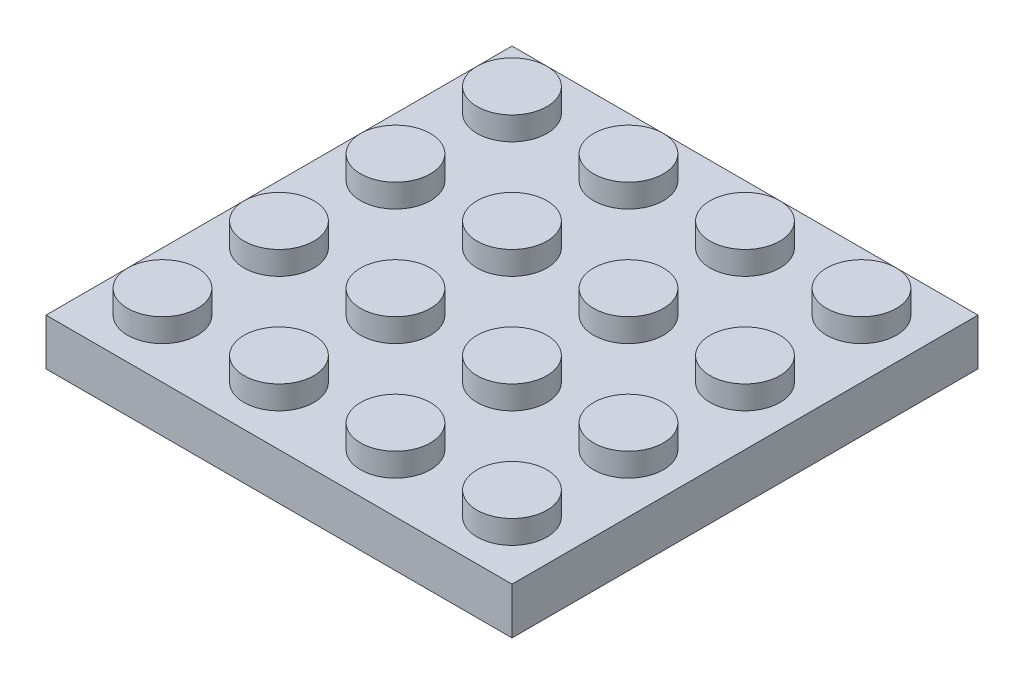
SolidWorks part; units mm, degrees
ref_plane "Front Plane" through (0, 0, 0) normal (0, 0, 1) x (1, 0, 0)
ref_plane "Top Plane" through (0, 0, 0) normal (0, 1, 0) x (1, 0, 0)
ref_plane "Right Plane" through (0, 0, 0) normal (1, 0, 0) x (0, 0, -1)
sketch "Sketch1" plane through (0, 0, 0) normal (0, 1, 0) x (1, 0, 0)
  line L0 (2.5, 12.5) -> (7.5, 17.5)
  line L1 (0, 0) -> (20, 0)
  line L2 (0, 0) -> (0, 20)
  line L3 (0, 20) -> (20, 20)
  line L4 (20, 0) -> (20, 20)
  line L5 (0, 20) -> (2.5, 20)
  line L6 (0, 20) -> (0, 17.5)
  line L7 (0, 17.5) -> (2.5, 17.5)
  line L8 (2.5, 20) -> (2.5, 17.5)
  line L9 (1, 1) -> (19, 1)
  line L10 (1, 1) -> (1, 19)
  line L11 (1, 19) -> (19, 19)
  line L12 (19, 1) -> (19, 19)
  line L13 (1, 1) -> (19, 19) construction
  line L14 (1, 19) -> (19, 1) construction
  circle A0 centre (2.5, 17.5) radius 1.5
  circle A1 centre (7.5, 17.5) radius 1.5
  circle A2 centre (12.5, 17.5) radius 1.5
  circle A3 centre (17.5, 17.5) radius 1.5
  circle A4 centre (2.5, 12.5) radius 1.5
  circle A5 centre (7.5, 12.5) radius 1.5
  circle A6 centre (12.5, 12.5) radius 1.5
  circle A7 centre (17.5, 12.5) radius 1.5
  circle A8 centre (2.5, 7.5) radius 1.5
  circle A9 centre (7.5, 7.5) radius 1.5
  circle A10 centre (12.5, 7.5) radius 1.5
  circle A11 centre (17.5, 7.5) radius 1.5
  circle A12 centre (2.5, 2.5) radius 1.5
  circle A13 centre (7.5, 2.5) radius 1.5
  circle A14 centre (12.5, 2.5) radius 1.5
  circle A15 centre (17.5, 2.5) radius 1.5
  circle A16 centre (5, 15) radius 2.0355
  circle A17 centre (10, 15) radius 2.0355
  circle A18 centre (15, 15) radius 2.0355
  circle A19 centre (10, 10) radius 2.0355
  circle A20 centre (15, 10) radius 2.0355
  circle A21 centre (10, 5) radius 2.0355
  circle A22 centre (15, 5) radius 2.0355
  circle A23 centre (5, 10) radius 2.0355
  circle A24 centre (5, 5) radius 2.0355
  circle A25 centre (5, 15) radius 1.5
  circle A26 centre (10, 15) radius 1.5
  circle A27 centre (15, 15) radius 1.5
  circle A28 centre (10, 10) radius 1.5
  circle A29 centre (15, 10) radius 1.5
  circle A30 centre (10, 5) radius 1.5
  circle A31 centre (15, 5) radius 1.5
  circle A32 centre (5, 10) radius 1.5
  circle A33 centre (5, 5) radius 1.5
  point P8 (10, 10)
  point P13 (10, 19)
  point P14 (10, 20)
  point P15 (1, 10)
  point P16 (0, 10)
  dimension "D8" = 3
  dimension "D1" = 20
  dimension "D2" = 2.5
  dimension "D3" = 1
  dimension "D4" = 4
  dimension "D5" = 4
  dimension "D6" = 3
  dimension "D7" = 3
  dimension "D9" = 3
  dimension "D10" = 3
extrude "Boss-Extrude1" add sketch "Sketch1" against normal blind 1 contours L12 L9 L10 L7 L2 L1 L4 L3 L8 L11 | A24 A33 | A23 A32 | A25 L0 A16 | A25 L0 A16 | A21 A30 | A22 A31 | A18 A27 | A20 A29 | A19 A28 | A17 A26 | L10 L11 L8 L3 L2 L7 region at (3.0136, 0, -15) region at (3.7847, 0, -13.7153) region at (0.7172, 0, -10) region at (5, 0, -11.978) region at (0.9688, 0, -19.0313) region at (8.022, 0, -15) region at (5, 0, -6.978) region at (10, 0, -11.978) region at (13.022, 0, -15) region at (10, 0, -6.978) region at (15, 0, -11.978) region at (15, 0, -6.978)
extrude "Boss-Extrude2" add sketch "Sketch1<3>" along normal blind 2 separate body contours A13 | A12 | A14 | A15 | A10 | A9 | A8 | A4 | A5 | A11 | A7 | A6 | L8 A0 L7 | L7 A0 L8 | A1 | A2 | A3 region at (3.8466, 0, -13.0578) region at (2.7122, 0, -17.2878) region at (7.5, 0, -12.5) region at (2.5, 0, -7.5) region at (1.8634, 0, -18.1366) region at (6.1534, 0, -18.0578) region at (2.5, 0, -2.5) region at (12.5, 0, -12.5) region at (7.5, 0, -7.5) region at (12.5, 0, -17.5) region at (7.5, 0, -2.5) region at (17.5, 0, -17.5) region at (17.5, 0, -12.5) region at (12.5, 0, -7.5) region at (12.5, 0, -2.5) region at (17.5, 0, -2.5) region at (17.5, 0, -7.5)
sketch "Sketch1<3>" plane through (0, 0, 0) normal (0, 1, 0) x (1, 0, 0) same geometry as "Sketch1"
extrude "Boss-Extrude3" add sketch "Sketch1<4>" along normal blind 1 contours L2 L1 L4 L3
sketch "Sketch1<4>" plane through (0, 0, 0) normal (0, 1, 0) x (1, 0, 0) same geometry as "Sketch1"
